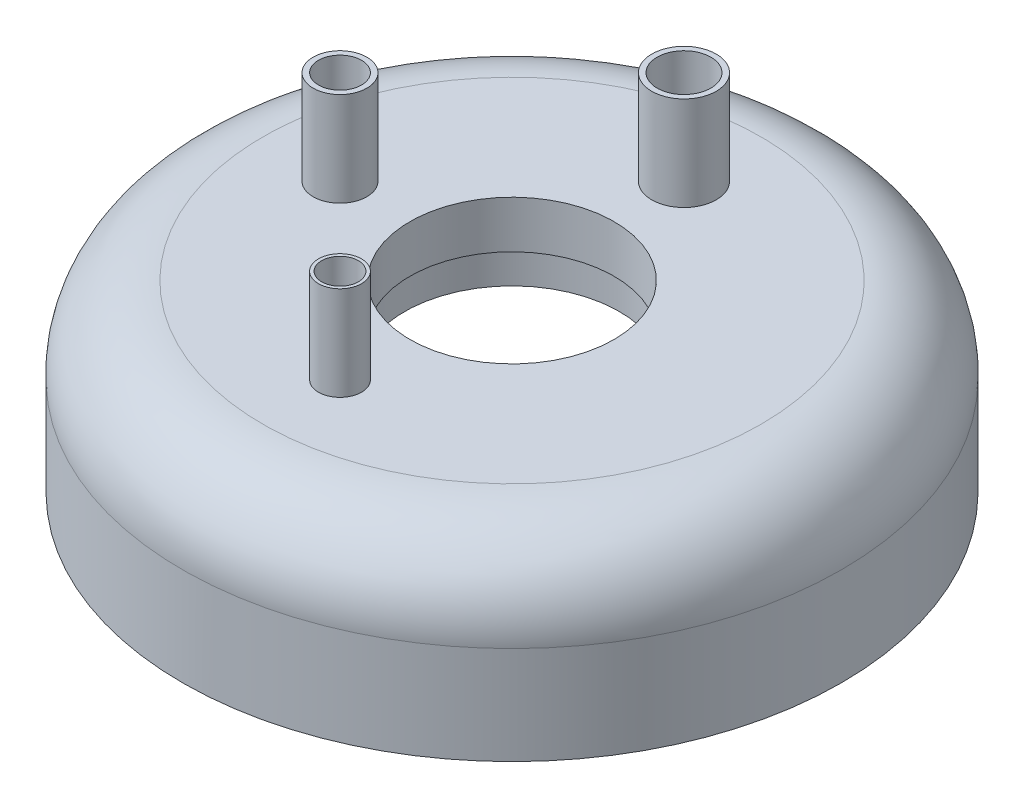
SolidWorks part; units mm, degrees
ref_plane "Front Plane" through (0, 0, 0) normal (0, 0, 1) x (1, 0, 0)
ref_plane "Top Plane" through (0, 0, 0) normal (0, 1, 0) x (1, 0, 0)
ref_plane "Right Plane" through (0, 0, 0) normal (1, 0, 0) x (0, 0, -1)
sketch "Sketch1" plane through (0, 0, 0) normal (0, 0, 1) x (1, 0, 0)
  line L0 (0, -1000) -> (0, 49000) construction
  line L1 (-19, 22.8037) -> (-46.3306, 22.8037)
  line L2 (-61.3, 6.8454) -> (-61.3, -11.3675)
  line L3 (-61.3, -11.3675) -> (-60, -11.3675)
  line L4 (-60, -11.3675) -> (-60, 6.9325)
  line L5 (-60, 6.9325) -> (-58.7, 6.9325)
  line L6 (-46.3306, 20.2037) -> (-21, 20.2037)
  line L9 (-19, 22.8037) -> (-19, 14.0037)
  line L10 (-20, 7.8037) -> (-21, 7.8037)
  line L11 (-21, 7.8037) -> (-21, 20.2037)
  line L12 (-20, 7.8037) -> (-20, 14.0037)
  line L13 (-20, 14.0037) -> (-19, 14.0037)
  arc A0 (-46.3306, 22.8037) -> (-61.3, 6.8454) centre (-46.3306, 7.8037) ccw
  arc A1 (-46.3306, 20.2037) -> (-58.7, 6.9325) centre (-46.3306, 7.8037) ccw
  dimension "D1" = 15
  dimension "D2" = 2.6
  dimension "D3" = 2.6
  dimension "D4" = 1.3
  dimension "D5" = 60
  dimension "D6" = 18.3
  dimension "D7" = 38
  dimension "D8" = 42
  dimension "D9" = 15
  dimension "D10" = 6.2
  dimension "D11" = 1
revolve "Revolve1" add sketch "Sketch1" angle 360 about L0
thread "Thread1" pitch 1.5 method cut profile "Thread Profile1" start angle 0, offset 0, length 20, pitch 1.5, diameter 120
ref_plane "Plane1" through (-60, 6.9325, 0) normal (0, 0, 1) x (-1, 0, 0)
sketch "Thread Profile1" plane through (-60, 6.9325, 0) normal (0, 0, 1) x (-1, 0, 0)
  line L0 (0, 0) -> (0, 1.5) construction
  line L1 (0, 0) -> (0.8119, 0.4687)
  line L2 (0.8119, 0.4687) -> (0.8119, 0.6562)
  line L3 (0.8119, 0.6562) -> (0, 1.125)
  line L4 (0.8119, 0.5625) -> (0, 0.5625) construction
  line L11 (0, 0) -> (0, 1.125)
  point P2 (0, 0)
  dimension "Pitch" = 1.5
  dimension "Profile_Angle" = 60
  dimension "Profile_Land" = 0.1875
  dimension "Profile_Height" = 0.8119
sketch "Sketch2" plane through (0, 22.8037, 0) normal (0, 1, 0) x (1, 0, 0)
  circle A0 centre (0, 32) radius 5
  circle A1 centre (0, 32) radius 6
  circle A2 centre (-32, 0) radius 4
  circle A3 centre (-32, 0) radius 5
  circle A4 centre (0, -32) radius 3.4163
  circle A5 centre (0, -32) radius 4
  dimension "D2" = 10
  dimension "D3" = 12
  dimension "D4" = 8
  dimension "D5" = 10
  dimension "D8" = 8
  dimension "D1" = 32
  dimension "D6" = 32
  dimension "D7" = 32
extrude "Boss-Extrude1" add sketch "Sketch2" along normal blind 17.5
sketch "Sketch3" plane through (0, 22.8037, 0) normal (0, 1, 0) x (1, 0, 0)
  circle A0 centre (0, 32) radius 5
  circle A1 centre (-32, 0) radius 4
  circle A2 centre (0, -32) radius 3.45
  dimension "D1" = 8
  dimension "D2" = 6.9
extrude "Cut-Extrude1" cut sketch "Sketch3" against normal blind 10
sketch "Sketch4" plane through (0, 0, 0) normal (0, 0, 1) x (1, 0, 0)
  line L0 (-61.3, -11.3675) -> (61.3, -11.3675) construction
  line L1 (-1, -9.1175) -> (1, -9.1175)
  line L2 (-1, -9.1175) -> (-1, -13.6175)
  line L3 (-1, -13.6175) -> (1, -13.6175)
  line L4 (1, -9.1175) -> (1, -13.6175)
  line L5 (-1, -9.1175) -> (1, -13.6175) construction
  line L6 (-1, -13.6175) -> (1, -9.1175) construction
  point P0 (0, -11.3675)
  dimension "D1" = 4.5
  dimension "D2" = 2
extrude "Cut-Extrude2" cut sketch "Sketch4" against normal blind 87
